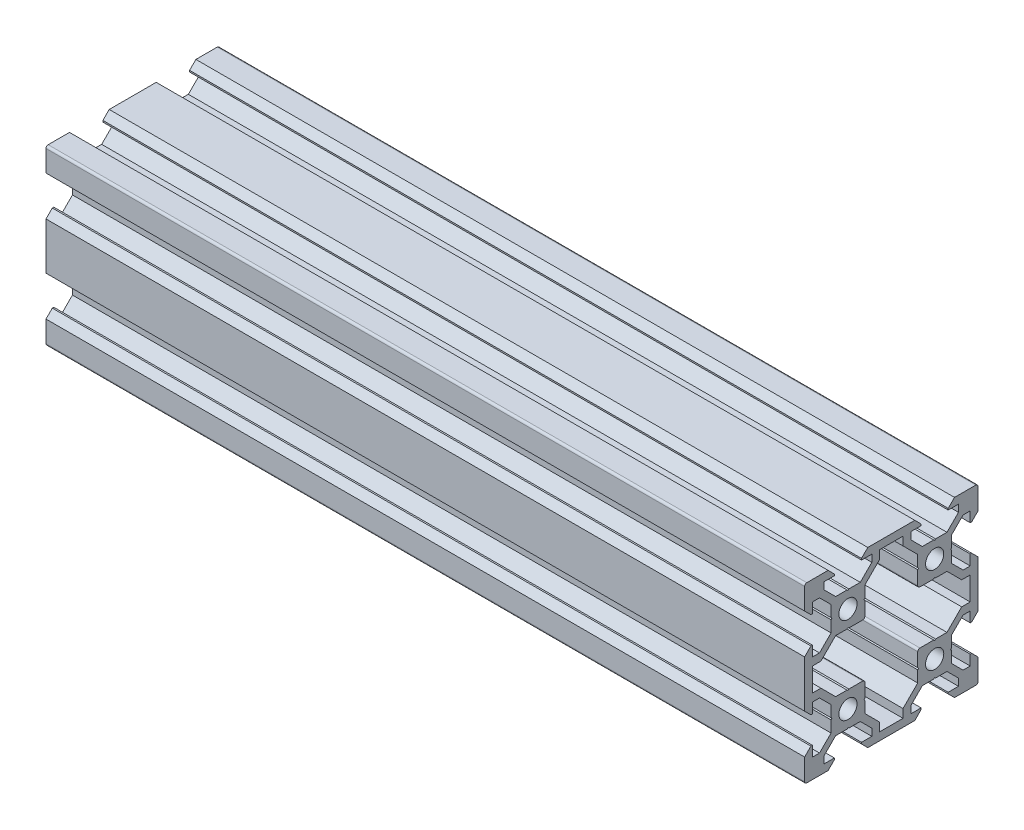
SolidWorks part; units mm, degrees
material "6061-T6 (SS)"
ref_plane "Top" through (0, 0, 0) normal (0, 0, 1) x (1, 0, 0)
ref_plane "Front" through (0, 0, 0) normal (0, 1, 0) x (1, 0, 0)
ref_plane "Right" through (0, 0, 0) normal (1, 0, 0) x (0, 0, -1)
sketch "Profile Sketch" plane through (0, 0, 0) normal (1, 0, 0) x (0, 0, -1)
  line L0 (0, 10) -> (-5.42, 10)
  line L1 (-4.5, 8.2) -> (-4.5, 6.56)
  line L2 (-4.5, 6.56) -> (-7.16, 3.9)
  line L3 (-7.16, 3.9) -> (-9.79, 3.9)
  line L4 (-9.79, 3.9) -> (-10, 3.69)
  line L5 (2.7, 8.2) -> (-2.7, 8.2)
  line L6 (-2.7, 8.2) -> (-2.7, 6.2387)
  line L7 (-2.7, 6.2387) -> (-6.1, 2.8387)
  line L8 (-6.1, 2.8387) -> (-6.1, 0.21)
  line L9 (-6.875, 8.545) -> (-6.875, 8.2)
  line L10 (-6.875, 8.2) -> (-4.5, 8.2)
  line L11 (-6.875, 8.545) -> (-5.42, 10)
  line L12 (0, -10) -> (0, 10) construction
  line L13 (-20, 0) -> (20, 0) construction
  line L14 (-10, -10) -> (-10, 10) construction
  line L21 (-6.6, -3.9) -> (-9.79, -3.9)
  line L25 (-10, 0) -> (-20, 10) construction
  line L26 (-18.545, 3.125) -> (-18.2, 3.125)
  line L31 (-16.2383, -7.3) -> (-12.84, -3.9)
  line L32 (-12.84, -3.9) -> (-10.21, -3.9)
  line L33 (-20, 4.58) -> (-20, 9.5)
  line L34 (-13.9, 2.8387) -> (-13.9, 0.21)
  line L35 (-16.56, 5.5) -> (-13.9, 2.8387)
  line L36 (-12.84, 3.9) -> (-10.21, 3.9)
  line L37 (-15.5, 6.56) -> (-12.84, 3.9)
  line L38 (-15.5, 8.2) -> (-15.5, 6.56)
  line L39 (-13.125, 8.545) -> (-14.58, 10)
  line L40 (-13.125, 8.2) -> (-15.5, 8.2)
  line L41 (-13.125, 8.545) -> (-13.125, 8.2)
  line L42 (-18.2, 3.125) -> (-18.2, 5.5)
  line L43 (-18.545, 3.125) -> (-20, 4.58)
  line L44 (-18.2, 5.5) -> (-16.56, 5.5)
  line L45 (-14.58, 10) -> (-19.5, 10)
  line L46 (-16.56, -5.5) -> (-13.9, -2.8387)
  line L48 (-18.2, -5.5) -> (-16.56, -5.5)
  line L49 (-18.545, -3.125) -> (-20, -4.58)
  line L50 (-18.2, -3.125) -> (-18.2, -5.5)
  line L51 (-20, -4.58) -> (-20, -15.42)
  line L52 (-18.545, -3.125) -> (-18.2, -3.125)
  line L53 (9.79, -3.9) -> (10, -3.69)
  line L99 (-10, 3.69) -> (-10.21, 3.9)
  line L100 (-10, -3.69) -> (-10.21, -3.9)
  line L101 (-9.79, -3.9) -> (-10, -3.69)
  line L102 (-13.9, -0.21) -> (-13.69, 0)
  line L103 (-13.69, 0) -> (-13.9, 0.21)
  line L104 (-13.9, -0.21) -> (-13.9, -2.8387)
  line L105 (-6.1, -0.21) -> (-6.31, 0)
  line L106 (-6.31, 0) -> (-6.1, -0.21)
  line L107 (-6.1, -0.21) -> (-6.1, -3.4)
  line L117 (-16.2383, -7.3) -> (-18.2, -7.3)
  line L118 (20, -10) -> (20, 10) construction
  line L119 (20, -10) -> (-20, -10) construction
  line L120 (-20, -10) -> (-20, 10) construction
  line L121 (20, 10) -> (-20, 10) construction
  line L122 (6.6, -3.9) -> (9.79, -3.9)
  line L123 (10, -3.69) -> (10.21, -3.9)
  line L124 (-18.2, -7.3) -> (-18.2, -12.7)
  line L125 (12.84, -3.9) -> (10.21, -3.9)
  line L126 (-6.31, 0) -> (-6.1, 0.21)
  line L127 (16.2383, -7.3) -> (12.84, -3.9)
  line L128 (20, -4.58) -> (20, -15.42)
  line L129 (18.2, -7.3) -> (18.2, -12.7)
  line L130 (16.2383, -7.3) -> (18.2, -7.3)
  line L131 (18.545, -3.125) -> (18.2, -3.125)
  line L132 (18.2, -3.125) -> (18.2, -5.5)
  line L133 (18.545, -3.125) -> (20, -4.58)
  line L134 (18.2, -5.5) -> (16.56, -5.5)
  line L135 (16.56, -5.5) -> (13.9, -2.8387)
  line L136 (13.9, -0.21) -> (13.9, -2.8387)
  line L137 (13.69, 0) -> (13.9, 0.21)
  line L138 (13.9, -0.21) -> (13.69, 0)
  line L139 (13.9, 2.8387) -> (13.9, 0.21)
  line L140 (18.2, 5.5) -> (16.56, 5.5)
  line L141 (18.545, 3.125) -> (20, 4.58)
  line L142 (18.2, 3.125) -> (18.2, 5.5)
  line L143 (16.56, 5.5) -> (13.9, 2.8387)
  line L144 (18.545, 3.125) -> (18.2, 3.125)
  line L145 (20, 4.58) -> (20, 9.5)
  line L146 (14.58, 10) -> (19.5, 10)
  line L147 (13.125, 8.545) -> (13.125, 8.2)
  line L148 (13.125, 8.2) -> (15.5, 8.2)
  line L149 (13.125, 8.545) -> (14.58, 10)
  line L150 (15.5, 8.2) -> (15.5, 6.56)
  line L151 (15.5, 6.56) -> (12.84, 3.9)
  line L152 (12.84, 3.9) -> (10.21, 3.9)
  line L153 (10, 3.69) -> (10.21, 3.9)
  line L154 (9.79, 3.9) -> (10, 3.69)
  line L155 (6.1, -0.21) -> (6.1, -3.4)
  line L156 (6.1, -0.21) -> (6.31, 0)
  line L157 (6.31, 0) -> (6.1, 0.21)
  line L158 (6.1, 2.8387) -> (6.1, 0.21)
  line L159 (7.16, 3.9) -> (9.79, 3.9)
  line L160 (2.7, 6.2387) -> (6.1, 2.8387)
  line L161 (4.5, 6.56) -> (7.16, 3.9)
  line L162 (6.875, 8.545) -> (6.875, 8.2)
  line L163 (6.875, 8.2) -> (4.5, 8.2)
  line L164 (4.5, 8.2) -> (4.5, 6.56)
  line L165 (2.7, 8.2) -> (2.7, 6.2387)
  line L166 (6.875, 8.545) -> (5.42, 10)
  line L167 (0, 10) -> (5.42, 10)
  line L168 (-20, -24.58) -> (-20, -29.5)
  line L169 (-14.58, -30) -> (-19.5, -30)
  line L170 (-7.16, -23.9) -> (-9.79, -23.9)
  line L171 (-10, -23.69) -> (-10.21, -23.9)
  line L172 (-9.79, -23.9) -> (-10, -23.69)
  line L173 (-12.84, -23.9) -> (-10.21, -23.9)
  line L174 (-13.125, -28.545) -> (-13.125, -28.2)
  line L175 (-13.125, -28.2) -> (-15.5, -28.2)
  line L176 (-13.125, -28.545) -> (-14.58, -30)
  line L177 (-15.5, -28.2) -> (-15.5, -26.56)
  line L178 (-15.5, -26.56) -> (-12.84, -23.9)
  line L179 (-18.2, -25.5) -> (-16.56, -25.5)
  line L180 (-18.545, -23.125) -> (-20, -24.58)
  line L181 (-18.2, -23.125) -> (-18.2, -25.5)
  line L182 (-16.56, -25.5) -> (-13.9, -22.8387)
  line L183 (-18.545, -23.125) -> (-18.2, -23.125)
  line L184 (-13.9, -19.79) -> (-13.9, -17.1613)
  line L185 (-13.69, -20) -> (-13.9, -20.21)
  line L186 (-13.9, -19.79) -> (-13.69, -20)
  line L187 (-13.9, -22.8387) -> (-13.9, -20.21)
  line L188 (-16.2383, -12.7) -> (-18.2, -12.7)
  line L189 (-18.545, -16.875) -> (-18.2, -16.875)
  line L190 (-18.2, -16.875) -> (-18.2, -14.5)
  line L191 (-18.545, -16.875) -> (-20, -15.42)
  line L192 (-18.2, -14.5) -> (-16.56, -14.5)
  line L193 (-16.56, -14.5) -> (-13.9, -17.1613)
  line L194 (-16.2383, -12.7) -> (-12.84, -16.1)
  line L195 (-9.79, -16.1) -> (-10, -16.31)
  line L196 (-10, -16.31) -> (-10.21, -16.1)
  line L197 (-12.84, -16.1) -> (-10.21, -16.1)
  line L198 (-6.6, -16.1) -> (-9.79, -16.1)
  line L199 (-6.1, -19.79) -> (-6.1, -16.6)
  line L200 (-6.1, -22.8387) -> (-6.1, -20.21)
  line L201 (-6.31, -20) -> (-6.1, -20.21)
  line L202 (-6.31, -20) -> (-6.1, -19.79)
  line L203 (-6.1, -19.79) -> (-6.31, -20)
  line L204 (-2.7, -26.2387) -> (-6.1, -22.8387)
  line L205 (-4.5, -26.56) -> (-7.16, -23.9)
  line L206 (-4.5, -28.2) -> (-4.5, -26.56)
  line L207 (-6.875, -28.2) -> (-4.5, -28.2)
  line L208 (-6.875, -28.545) -> (-6.875, -28.2)
  line L209 (-6.875, -28.545) -> (-5.42, -30)
  line L210 (0, -30) -> (-5.42, -30)
  line L211 (0, -30) -> (5.42, -30)
  line L212 (14.58, -30) -> (19.5, -30)
  line L213 (20, -24.58) -> (20, -29.5)
  line L214 (6.875, -28.545) -> (5.42, -30)
  line L215 (2.7, -28.2) -> (2.7, -26.2387)
  line L216 (4.5, -28.2) -> (4.5, -26.56)
  line L217 (6.875, -28.2) -> (4.5, -28.2)
  line L218 (6.875, -28.545) -> (6.875, -28.2)
  line L219 (4.5, -26.56) -> (7.16, -23.9)
  line L220 (2.7, -26.2387) -> (6.1, -22.8387)
  line L221 (7.16, -23.9) -> (9.79, -23.9)
  line L222 (6.1, -22.8387) -> (6.1, -20.21)
  line L223 (9.79, -23.9) -> (10, -23.69)
  line L224 (10, -23.69) -> (10.21, -23.9)
  line L225 (12.84, -23.9) -> (10.21, -23.9)
  line L226 (15.5, -26.56) -> (12.84, -23.9)
  line L227 (15.5, -28.2) -> (15.5, -26.56)
  line L228 (13.125, -28.545) -> (14.58, -30)
  line L229 (13.125, -28.2) -> (15.5, -28.2)
  line L230 (13.125, -28.545) -> (13.125, -28.2)
  line L231 (18.545, -23.125) -> (18.2, -23.125)
  line L232 (16.56, -25.5) -> (13.9, -22.8387)
  line L233 (18.2, -23.125) -> (18.2, -25.5)
  line L234 (18.545, -23.125) -> (20, -24.58)
  line L235 (18.2, -25.5) -> (16.56, -25.5)
  line L236 (13.9, -22.8387) -> (13.9, -20.21)
  line L237 (2.7, -28.2) -> (-2.7, -28.2)
  line L238 (6.31, -20) -> (6.1, -20.21)
  line L239 (6.1, -19.79) -> (6.31, -20)
  line L240 (13.9, -19.79) -> (13.69, -20)
  line L241 (13.69, -20) -> (13.9, -20.21)
  line L242 (6.1, -19.79) -> (6.1, -16.6)
  line L243 (13.9, -19.79) -> (13.9, -17.1613)
  line L244 (16.56, -14.5) -> (13.9, -17.1613)
  line L245 (18.2, -14.5) -> (16.56, -14.5)
  line L246 (18.545, -16.875) -> (20, -15.42)
  line L247 (18.2, -16.875) -> (18.2, -14.5)
  line L248 (18.545, -16.875) -> (18.2, -16.875)
  line L249 (16.2383, -12.7) -> (18.2, -12.7)
  line L250 (16.2383, -12.7) -> (12.84, -16.1)
  line L251 (12.84, -16.1) -> (10.21, -16.1)
  line L252 (10, -16.31) -> (10.21, -16.1)
  line L253 (6.6, -16.1) -> (9.79, -16.1)
  line L254 (9.79, -16.1) -> (10, -16.31)
  line L255 (-2.7, -26.2387) -> (-2.7, -28.2)
  circle A0 centre (-10, 0) radius 2.1
  arc A1 (-19.5, 10) -> (-20, 9.5) centre (-19.5, 9.5) ccw
  arc A2 (-6.6, -3.9) -> (-6.1, -3.4) centre (-6.6, -3.4) ccw
  arc A3 (6.6, -3.9) -> (6.1, -3.4) centre (6.6, -3.4) cw
  circle A4 centre (10, 0) radius 2.1
  arc A5 (19.5, 10) -> (20, 9.5) centre (19.5, 9.5) cw
  arc A6 (-19.5, -30) -> (-20, -29.5) centre (-19.5, -29.5) cw
  arc A7 (-6.6, -16.1) -> (-6.1, -16.6) centre (-6.6, -16.6) cw
  arc A8 (19.5, -30) -> (20, -29.5) centre (19.5, -29.5) ccw
  circle A9 centre (10, -20) radius 2.1
  arc A10 (6.6, -16.1) -> (6.1, -16.6) centre (6.6, -16.6) ccw
  circle A11 centre (-10, -20) radius 2.1
  point P35 (-2.4957, 0)
  point P119 (0, 18.9743)
  point P121 (0, 8.2)
  point P123 (2.4957, 0)
  point P131 (0, 0)
  point P143 (0, 0)
  point P164 (-18.2, -10)
  point P234 (18.2, -10)
  dimension "D4" = 5.42
  dimension "D5" = 40
  dimension "D6" = 4.2
  dimension "D16" = 0.5
  dimension "D17" = 0.5
  dimension "D2" = 45
  dimension "D3" = 20
  dimension "D7" = 1.5
  dimension "D9" = 10
  dimension "D10" = 3.9
  dimension "D11" = 3.9
  dimension "D13" = 3.125
  dimension "D14" = 5.5
  dimension "D15" = 1.64
  dimension "Knotch Depth" = 0.21
extrude "Profile Extrude" add sketch "Profile Sketch" along normal blind 175 contours L0 L11 L9 L10 L1 L2 L3 L4 L99 L36 L37 L38 L40 L41 L39 L45 A1 L33 L43 L26 L42 L44 L35 L34 L103 L102 L104 L46 L48 L50 L52 L49 L51 region at (0, 9.4343, -2.71)
equation "\"M2x0.4_Close_Hole\"= 2.2"
equation "\"M2.5x0.45_Close_Hole\"= 2.7"
equation "\"M3x0.5_Close_Hole\"= 3.2"
equation "\"M4x0.7_Close_Hole\"= 4.3"
equation "\"M5x0.8_Close_Hole\"= 5.3"
equation "\"M6x1_Close_Hole\"= 6.3"
equation "\"M7x1_Close_Hole\"= 7.4"
equation "\"M8x1.25_Close_Hole\"= 8.4"
equation "\"M2x0.4_Tap_Hole_75\"= 1.6"
equation "\"M3x0.5_Tap_Hole_75\"= 2.5"
equation "\"M4x0.7_Tap_Hole_75\"= 3.3"
equation "\"M5x0.8_Tap_Hole_75\"= 4.2"
equation "\"M6x1_Tap_Hole_75\"= 5"
equation "\"M7x1_Tap_Hole_75\"= 6"
equation "\"M8x1.25_Tap_Hole_75\"= 6.8"
